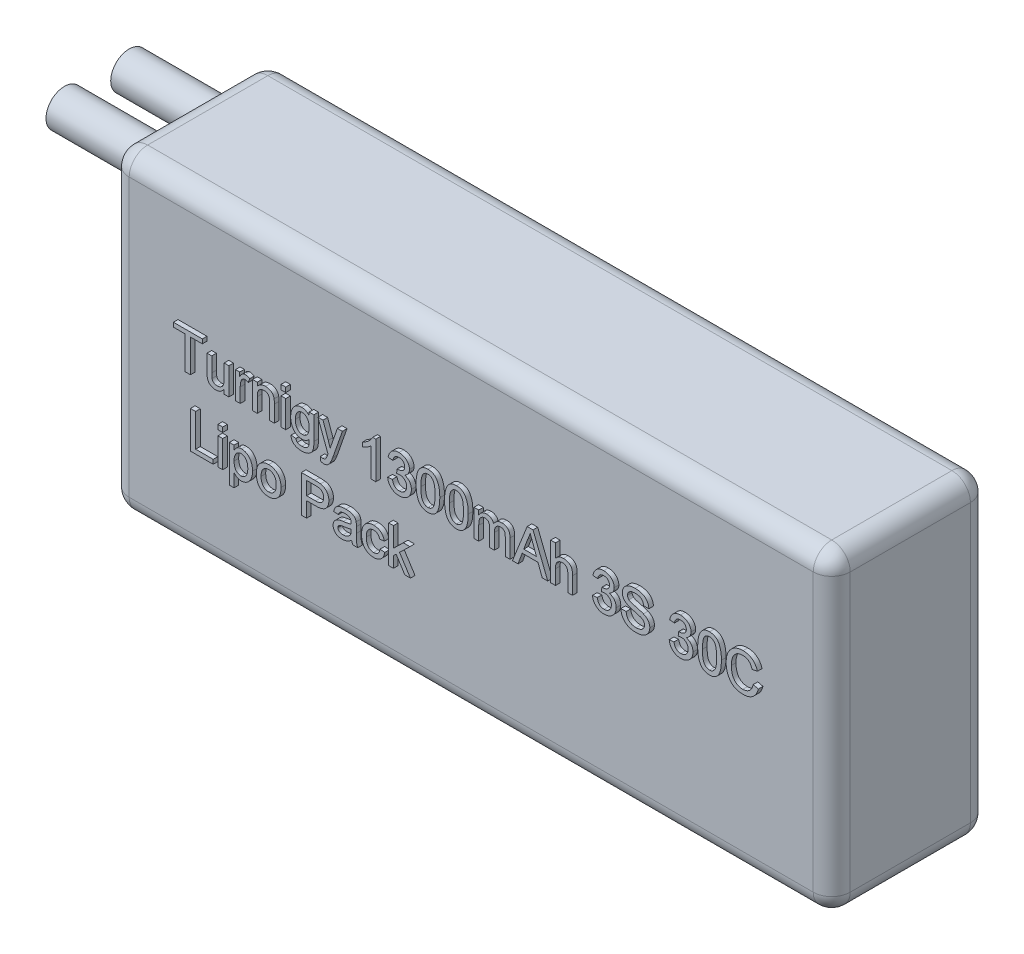
SolidWorks part; units mm, degrees
ref_plane "Спереди" through (0, 0, 0) normal (0, 0, 1) x (1, 0, 0)
ref_plane "Сверху" through (0, 0, 0) normal (0, 1, 0) x (1, 0, 0)
ref_plane "Справа" through (0, 0, 0) normal (1, 0, 0) x (0, 0, -1)
sketch "Эскиз1" plane through (0, 0, 0) normal (0, 0, 1) x (1, 0, 0)
  line L1 (-39, 17) -> (39, 17)
  line L2 (-39, 17) -> (-39, -17)
  line L3 (-39, -17) -> (39, -17)
  line L4 (39, 17) -> (39, -17)
  line L5 (-39, 17) -> (39, -17) construction
  line L6 (-39, -17) -> (39, 17) construction
  point P0 (0, 0)
  dimension "D1" = 78
  dimension "D2" = 34
extrude "Бобышка-Вытянуть1" add sketch "Эскиз1" along normal mid plane 17
sketch "Эскиз2" plane through (-39, 0, 0) normal (-1, 0, 0) x (0, 0, 1)
  line L0 (-3.5, 13) -> (3.5, 13) construction
  line L1 (0, 13) -> (0, 17) construction
  line L2 (8.5, 17) -> (-8.5, 17) construction
  circle A0 centre (-3.5, 13) radius 2
  circle A1 centre (3.5, 13) radius 2
  dimension "D1" = 4
  dimension "D2" = 7
  dimension "D3" = 4
extrude "Бобышка-Вытянуть2" add sketch "Эскиз2" along normal blind 10
sketch "Эскиз3" plane through (0, 0, 8.5) normal (0, 0, 1) x (1, 0, 0)
  text T0 "Turnigy 1300mAh 3S 30C\r\n Lipo Pack"
extrude "Бобышка-Вытянуть3" add sketch "Эскиз3" along normal blind 0.5
fillet "Redondeo2" radius 2 12 edges at (-39, 17, 0) (-39, -17, 0) (39, 17, 0) (39, -17, 0) (39, 0, 8.5) (0, -17, 8.5) (0, 17, 8.5) (-39, 0, 8.5) (-39, 0, -8.5) (0, -17, -8.5) (39, 0, -8.5) (0, 17, -8.5)
